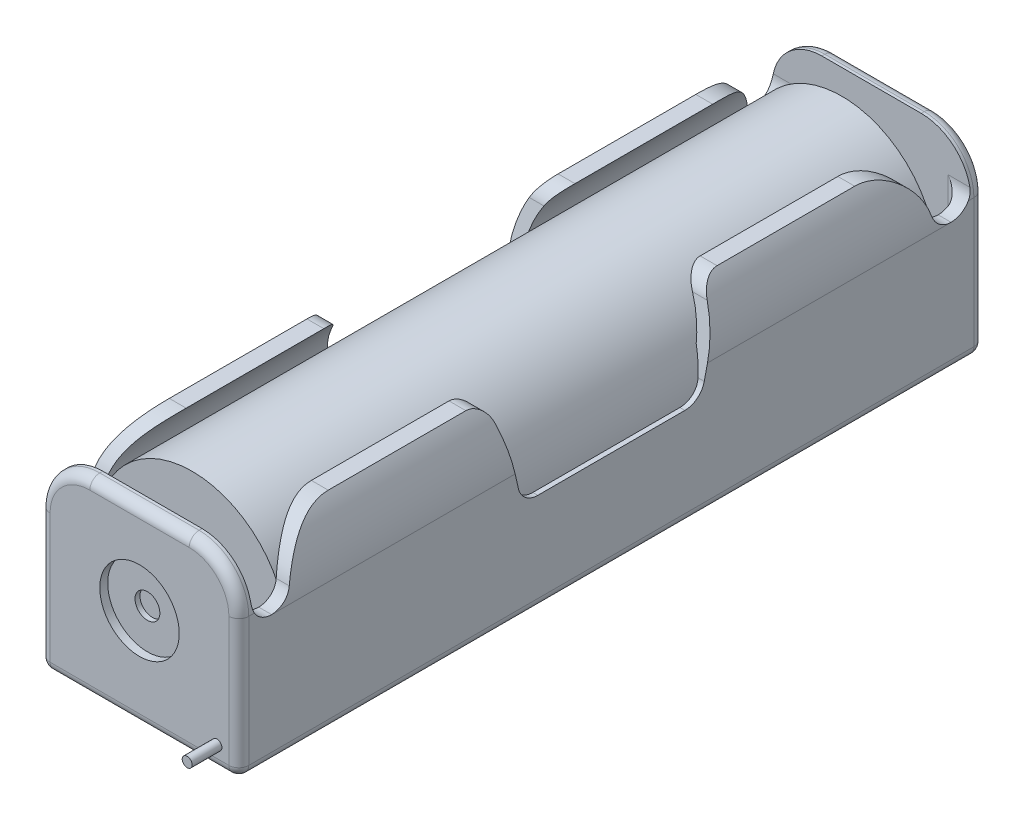
SolidWorks part; units mm, degrees
ref_plane "Front" through (0, 0, 0) normal (0, 0, 1) x (1, 0, 0)
ref_plane "Top" through (0, 0, 0) normal (0, 1, 0) x (1, 0, 0)
ref_plane "Right" through (0, 0, 0) normal (1, 0, 0) x (0, 0, -1)
sketch "草图1" plane through (0, 0, 0) normal (0, 0, 1) x (1, 0, 0)
  line L1 (0, 0) -> (20, 0)
  line L2 (0, 0) -> (0, 13)
  line L4 (20, 0) -> (20, 13)
  arc A0 (20, 13) -> (0, 13) centre (10, 13) ccw
  dimension "D1" = 20
  dimension "D2" = 13
extrude "凸台-拉伸1" add sketch "草图1" along normal blind 75
shell "抽壳1" thickness 1.3 removed face at (10, 0, 37.5)
sketch "草图2" plane through (0, 0, 0) normal (0, -1, 0) x (1, 0, 0)
  line L0 (0, 75) -> (20, 75) construction
  line L1 (18.7, 73.7) -> (1.3, 73.7)
  line L2 (18.7, 73.7) -> (18.7, 1.3)
  line L3 (18.7, 1.3) -> (1.3, 1.3)
  line L4 (1.3, 73.7) -> (1.3, 1.3)
  line L5 (14, 73.5) -> (6, 73.5)
  line L6 (14, 73.5) -> (14, 71.7)
  line L7 (14, 71.7) -> (6, 71.7)
  line L8 (6, 73.5) -> (6, 71.7)
  line L9 (0, 0) -> (20, 0) construction
  line L10 (14, 3.3) -> (6, 3.3)
  line L11 (14, 3.3) -> (14, 1.5)
  line L12 (14, 1.5) -> (6, 1.5)
  line L13 (6, 3.3) -> (6, 1.5)
  circle A0 centre (10, 37.5) radius 1
  point P12 (10, 73.5)
  point P13 (10, 73.7)
  dimension "D1" = 8
  dimension "D2" = 1.8
  dimension "D3" = 1.5
  dimension "D4" = 0
  dimension "D5" = 1.5
  dimension "D6" = 1.8
extrude "凸台-拉伸2" add sketch "草图2" against normal blind 1.3
sketch "草图3" plane through (0, 0, 0) normal (0, 0, -1) x (-1, 0, 0)
  line L0 (0, 0) -> (-20, 0) construction
  line L1 (-25.8685, 34.198) -> (7.5448, 34.198)
  line L2 (-25.8685, 34.198) -> (-25.8685, 19)
  line L3 (-25.8685, 19) -> (7.5448, 19)
  line L4 (7.5448, 34.198) -> (7.5448, 19)
  dimension "D1" = 19
extrude "切除-拉伸1" cut sketch "草图3" against normal through all
sketch "草图4" plane through (20, 0, 0) normal (1, 0, 0) x (0, 0, -1)
  line L0 (-49.5, 23.1993) -> (-25.5, 23.1993)
  line L1 (-25.5, 23.1993) -> (-28.5, 10)
  line L2 (-28.5, 10) -> (-46.5, 10)
  line L3 (-46.5, 10) -> (-49.5, 23.1993)
  line L4 (-75, 0) -> (0, 0) construction
  point P6 (-37.5, 0)
  point P7 (-37.5, 10)
  dimension "D1" = 18
  dimension "D2" = 10
  dimension "D3" = 0
  dimension "D4" = 3
  dimension "D5" = 3
extrude "切除-拉伸3" cut sketch "草图4" against normal through all
sketch "草图5" plane through (20, 0, 0) normal (1, 0, 0) x (0, 0, -1)
  line L0 (-27.8181, 13) -> (0, 13) construction
  line L1 (-75, 13) -> (-47.1819, 13) construction
  line L2 (0, 0) -> (0, 13) construction
  line L3 (-75, 0) -> (-75, 13) construction
  line L4 (-70, 13) -> (-75, 13)
  line L5 (-75, 13) -> (-82.2037, 25.5238)
  line L6 (-82.2037, 25.5238) -> (-64, 27.6609)
  line L7 (-64, 27.6609) -> (-64, 19)
  line L8 (-5, 13) -> (0, 13)
  line L9 (0, 13) -> (7.9098, 22.3734)
  line L10 (7.9098, 22.3734) -> (-6.7017, 29.489)
  line L11 (-6.7017, 29.489) -> (-11, 19)
  arc A0 (-5, 13) -> (-11, 19) centre (-11, 13) ccw
  arc A1 (-64, 19) -> (-70, 13) centre (-64, 13) ccw
  dimension "D1" = 11
  dimension "D2" = 11
extrude "切除-拉伸4" cut sketch "草图5" against normal through all
sketch "草图6" plane through (0, 13, 0) normal (0, 1, 0) x (1, 0, 0)
  line L1 (20, -75) -> (0, -75)
  line L5 (0, -5) -> (0, 0) construction
  line L6 (20, 0) -> (0, 0)
  line L7 (20, 0) -> (20, -1.3)
  line L8 (20, -1.3) -> (0, -1.3)
  line L9 (0, 0) -> (0, -1.3)
  line L10 (0, -75) -> (0, -73.7)
  line L11 (0, -75) -> (0, -70) construction
  line L12 (0, -73.7) -> (20, -73.7)
  line L13 (20, -75) -> (20, -70) construction
  line L14 (20, -73.7) -> (20, -75)
extrude "凸台-拉伸3" add sketch "草图6" along normal blind 6
fillet "圆角3" radius 5 4 edges at (0, 19, 0.65) (20, 19, 0.65) (20, 19, 74.35) (0, 19, 74.35)
fillet "圆角4" radius 2 4 edges at (0.65, 13, 73.7) (19.35, 13, 73.7) (19.35, 13, 1.3) (0.65, 13, 1.3)
fillet "圆角5" radius 2 4 edges at (19.35, 13, 5) (0.65, 13, 5) (0.65, 13, 70) (19.35, 13, 70)
fillet "圆角6" radius 2 8 edges at (19.35, 10, 28.5) (17.15, 19, 26.4544) (0.65, 10, 28.5) (2.85, 19, 26.4544) (0.65, 10, 46.5) (2.85, 19, 48.5456) (19.35, 10, 46.5) (17.15, 19, 48.5456)
fillet "圆角7" radius 1 16 edges at (0, 7, 0) (1.4645, 17.5355, 0) (10, 19, 0) (20, 7, 0) (0, 7, 75) (1.4645, 17.5355, 75) (10, 19, 75) (18.5355, 17.5355, 75) (10, 0, 75) (18.5355, 17.5355, 0) (20, 7, 75) (20, 0, 37.5) (18.7, 8.15, 1.3) (1.3, 8.15, 1.3) (0, 0, 37.5) (10, 0, 0)
sketch "草图7" plane through (0, 0, 75) normal (0, 0, 1) x (1, 0, 0)
  line L0 (19, 0) -> (1, 0) construction
  circle A0 centre (10, 10) radius 4
  dimension "D1" = 10
extrude "切除-拉伸5" cut sketch "草图7" against normal blind 0.8
sketch "草图8" plane through (0, 0, 1.3) normal (0, 0, 1) x (1, 0, 0)
  circle A0 centre (10, 10) radius 1.25
extrude "切除-拉伸7" cut sketch "草图8" against normal through all both and the other way through all contours A0
sketch "草图9" plane through (0, 0, 0) normal (0, 0, -1) x (-1, 0, 0)
  circle A0 centre (-10, 10) radius 4
extrude "切除-拉伸8" cut sketch "草图9" against normal blind 0.8
sketch "草图10" plane through (0, 0, 73.7) normal (0, 0, -1) x (-1, 0, 0)
  circle A0 centre (-10, 10) radius 2
extrude "凸台-拉伸4" add sketch "草图10" along normal blind 4
sketch "草图11" plane through (0, 0, 1.3) normal (0, 0, 1) x (1, 0, 0)
  circle A0 centre (10, 10) radius 4
  dimension "D1" = 8
extrude "凸台-拉伸5" add sketch "草图11" along normal blind 3
sketch "草图12" plane through (0, 0, 69.7) normal (0, 0, -1) x (-1, 0, 0)
  circle A0 centre (-10, 10) radius 9.5
  dimension "D1" = 19
extrude "凸台-拉伸6" add sketch "草图12" along normal up to surface (65.4 mm away) up to face at (14, 10, 4.3)
sketch "草图13" plane through (0, 0, 0) normal (0, 0, -1) x (-1, 0, 0)
  line L0 (0, 14) -> (0, 1) construction
  line L1 (-1, 0) -> (-19, 0) construction
  circle A0 centre (-2.2, 2.2) radius 0.5
  dimension "D1" = 2.2
  dimension "D2" = 1
  dimension "D3" = 2.2
extrude "凸台-拉伸7" add sketch "草图13" along normal blind 3 contours A0
sketch "草图14" plane through (0, 0, 75) normal (0, 0, 1) x (1, 0, 0)
  line L0 (20, 14) -> (20, 1) construction
  line L1 (19, 0) -> (1, 0) construction
  circle A0 centre (17.8, 2.2) radius 0.5
  dimension "D1" = 2.2
  dimension "D2" = 2.2
extrude "凸台-拉伸8" add sketch "草图14" along normal blind 3
